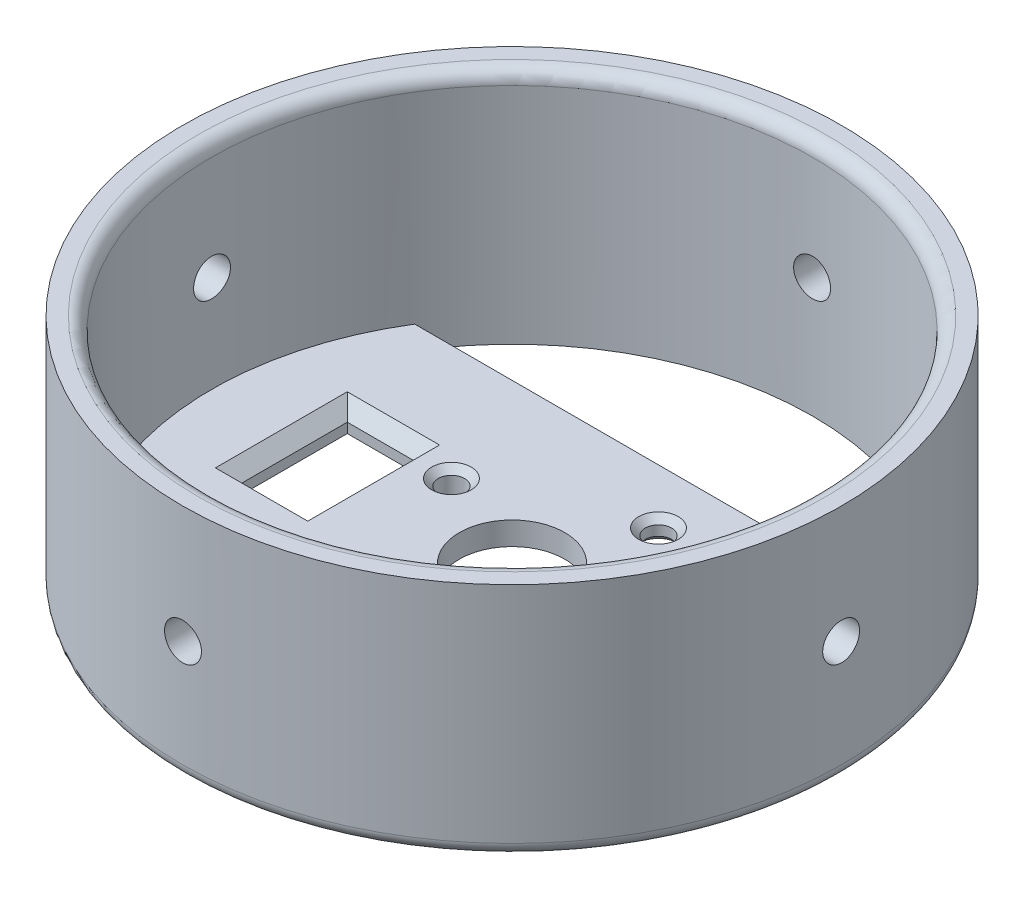
SolidWorks part; units mm, degrees
ref_plane "Front Plane" through (0, 0, 0) normal (0, 0, 1) x (1, 0, 0)
ref_plane "Top Plane" through (0, 0, 0) normal (0, 1, 0) x (1, 0, 0)
ref_plane "Right Plane" through (0, 0, 0) normal (1, 0, 0) x (0, 0, -1)
sketch "Sketch1" plane through (0, 0, 0) normal (0, 1, 0) x (1, 0, 0)
  line L0 (0, 8.5) -> (0, -8.5) construction
  line L1 (3.2528, 7.853) -> (-3.2528, -7.853) construction
  circle A0 centre (0, 0) radius 25
  circle A1 centre (0, 0) radius 4
  circle A2 centre (0, 0) radius 8.5 construction
  circle A3 centre (3.2528, 7.853) radius 1
  circle A4 centre (7.853, -3.2528) radius 1
  circle A5 centre (-3.2528, -7.853) radius 1
  circle A6 centre (-7.853, 3.2528) radius 1
  point P19 (0, 0)
  dimension "D1" = 50
  dimension "D2" = 8
  dimension "D3" = 17
  dimension "D5" = 2
  dimension "D4" = 22.5
  dimension "D6" = 4
extrude "Main Boss" add sketch "Sketch1" along normal blind 18
sketch "Sketch2" plane through (0, 18, 0) normal (0, 1, 0) x (1, 0, 0)
  circle A0 centre (0, 0) radius 22.8
  dimension "D1" = 45.6
extrude "Hollow" cut sketch "Sketch2" against normal offset from surface (16.25 mm away) 1.75 up to face at (0, 0, 25)
fillet "Fillet1" radius 1 2 edges at (0, 0, 25) (0, 18, 22.8)
sketch "Sketch3" plane through (0, 0, 0) normal (0, 0, 1) x (1, 0, 0)
  line L0 (25, 18) -> (-25, 18) construction
  circle A0 centre (0, 9.1) radius 1.4
  dimension "D2" = 2.8
  dimension "D1" = 8.9
extrude "External Screw Holes" cut sketch "Sketch3" against normal through all both and the other way through all
pattern_circular "CirPattern1" count 2 every 90 about axis through (0, -64.4881, 0) along (0, 1, 0) of "External Screw Holes"
sketch "Sketch4" plane through (0, 1.75, 0) normal (0, 1, 0) x (1, 0, 0)
  line L0 (-18.7307, 13) -> (18.7307, 13)
  line L1 (-18.7307, -13) -> (18.7307, -13)
  circle A0 centre (0, 0) radius 22.8 construction
  arc A1 (-18.7307, -13) -> (18.7307, -13) centre (0, 0) ccw
  arc A2 (18.7307, 13) -> (-18.7307, 13) centre (0, 0) ccw
  dimension "D1" = 26
extrude "Sensor Allowance" cut sketch "Sketch4" against normal through all
sketch "Sketch5" plane through (0, 1.75, 0) normal (0, 1, 0) x (1, 0, 0)
  line L0 (-16.5, 0) -> (16.5, 0) construction
  line L1 (-16.5, 4) -> (-11.5, 4)
  line L2 (-16.5, 4) -> (-16.5, -4)
  line L3 (-16.5, -4) -> (-11.5, -4)
  line L4 (-11.5, 4) -> (-11.5, -4)
  line L5 (11.5, 4) -> (16.5, 4)
  line L6 (11.5, 4) -> (11.5, -4)
  line L7 (11.5, -4) -> (16.5, -4)
  line L8 (16.5, 4) -> (16.5, -4)
  dimension "D1" = 5
  dimension "D2" = 8
  dimension "D3" = 23
extrude "Power Allowance" cut sketch "Sketch5" against normal through all
sketch "Sketch7" plane through (0, 0, 0) normal (0, -1, 0) x (1, 0, 0)
  line L0 (-12.5, -18.5) -> (1.75, -18.5)
  line L1 (-12.5, -18.5) -> (-12.5, -13)
  line L2 (1.75, -18.5) -> (1.75, -13)
  line L3 (-12.5, -13) -> (1.75, -13)
  line L4 (12.5, 13) -> (-1.75, 13)
  line L5 (12.5, -13) -> (12.5, -18.5)
  line L6 (12.5, -13) -> (2.25, -13)
  line L7 (12.5, -18.5) -> (2.25, -18.5)
  line L8 (2.25, -13) -> (2.25, -18.5)
  line L9 (-18.7307, -13) -> (18.7307, -13) construction
  line L10 (12.5, 18.5) -> (12.5, 13)
  line L11 (12.5, 18.5) -> (-1.75, 18.5)
  line L12 (-1.75, 18.5) -> (-1.75, 13)
  line L13 (-2.25, 13) -> (-2.25, 18.5)
  line L14 (-12.5, 13) -> (-2.25, 13)
  line L15 (-12.5, 18.5) -> (-2.25, 18.5)
  line L16 (-12.5, 13) -> (-12.5, 18.5)
  line L17 (18.7307, 13) -> (-18.7307, 13) construction
  line L18 (-12.5, -18.5) -> (-13.3263, -18.5) construction
  line L19 (12.5, -18.5) -> (13.3263, -18.5) construction
  line L20 (-12.5, 18.5) -> (-13.3263, 18.5) construction
  line L21 (12.5, 18.5) -> (13.3263, 18.5) construction
  arc A0 (-18.7307, -13) -> (18.7307, -13) centre (0, 0) ccw construction
  arc A1 (18.7307, 13) -> (-18.7307, 13) centre (0, 0) ccw construction
  point P23 (0, 0)
  dimension "D1" = 5.5
  dimension "D2" = 14.25
  dimension "D3" = 10.25
  dimension "D5" = 0.5
  dimension "D4" = 2
chamfer "Chamfer1" distance 1 angle 45 10 edges at (-14, 1.75, -4) (-16.5, 1.75, 0) (-14, 1.75, 4) (-11.5, 1.75, 0) (14, 1.75, -4) (16.5, 1.75, 0) (14, 1.75, 4) (11.5, 1.75, 0) (0, 1.75, -13) (0, 1.75, 13)
chamfer "Chamfer2" distance 0.5 angle 45 5 edges at (3.2528, 1.75, -6.853) (3.2528, 0, -6.853) (-3.2528, 1.75, 8.853) (7.853, 1.75, 4.2528) (-7.853, 1.75, -2.2528)
